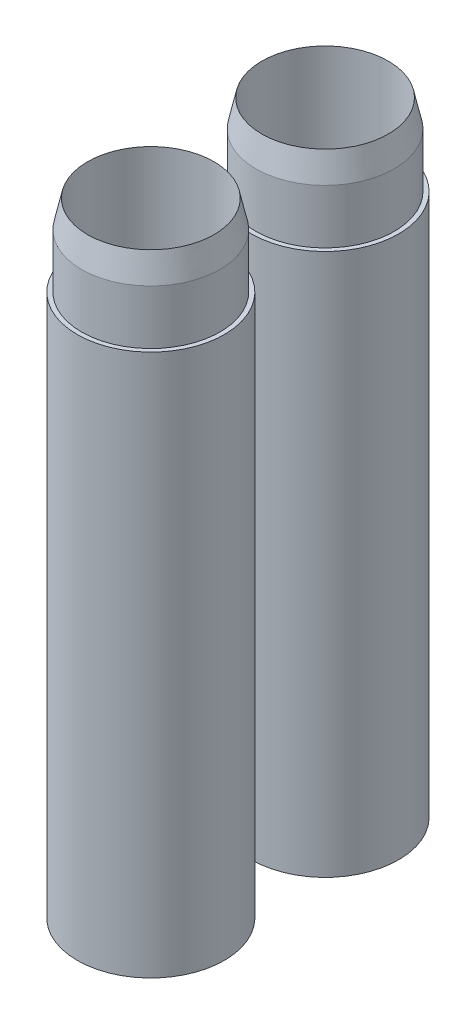
SolidWorks part; units mm, degrees
other "DetailItem1"
other "DetailItem2"
material "PLA"
ref_plane "Front Plane" through (0, 0, 0) normal (0, 0, 1) x (1, 0, 0)
ref_plane "Top Plane" through (0, 0, 0) normal (0, 1, 0) x (1, 0, 0)
ref_plane "Right Plane" through (0, 0, 0) normal (1, 0, 0) x (0, 0, -1)
sketch "Sketch1" plane through (0, 0, 0) normal (0, 1, 0) x (1, 0, 0)
  line L0 (-25.4274, 2.5) -> (-26.75, 0)
  line L1 (-26.75, 0) -> (-25.4274, -2.5)
  circle A0 centre (0, 0) radius 27.15
  arc A1 (-25.4274, -2.5) -> (-25.4274, 2.5) centre (0, 0) ccw
  dimension "D1" = 54.3
  dimension "D2" = 1.6
  dimension "D3" = 26.75
  dimension "D4" = 5
extrude "mandrel" add sketch "Sketch1" along normal blind 200 contours A0 A1 L1 L0 region at (-27.0732, 0, 0)
ref_axis "x" through (-29.7, 0, 0) along (1, 0, 0)
ref_axis "y" through (0, 200, 0) along (0, -1, 0)
ref_axis "z" through (0, 0, -29.7) along (0, 0, 1)
ref_axis "rip_tab_edge" through (-25.4274, 200, 2.5) along (0, -1, 0)
ref_plane "Plane3" through (0, 0, 0) normal (0, 0, -1) x (-1, 0, 0)
ref_plane "Plane2" through (0, 0, 0) normal (-0.0978, 0, -0.9952) x (-0.9952, 0, 0.0978)
sketch "Sketch3" plane through (0, 0, 0) normal (-0.0978, 0, -0.9952) x (-0.9952, 0, 0.0978)
  line L0 (25.55, 0) -> (20.55, 8.6603)
  line L1 (20.55, 8.6603) -> (20.55, 18.6603)
  line L2 (20.55, 18.6603) -> (25.55, 27.3205)
  line L3 (25.55, 200) -> (25.55, 0) construction
  line L4 (25.55, 27.3205) -> (25.55, 0)
  dimension "D1" = 5
  dimension "D2" = 30
  dimension "D3" = 30
  dimension "D4" = 10
sketch "Sketch4" plane through (0, 0, 0) normal (0, 0, -1) x (-1, 0, 0)
  line L2 (-23.3331, 192.2169) -> (-23.3331, 230)
  line L4 (-25.55, 190) -> (-25.55, 220)
  line L10 (-25.55, 220) -> (-23.3331, 230)
  line L11 (-23.3331, 192.2169) -> (-25.55, 190)
  line L12 (27.15, 200) -> (-27.15, 200) construction
  dimension "D2" = 25.55
  dimension "D3" = 30
  dimension "D1" = 135
  dimension "D4" = 12.5
  dimension "D5" = 10
  dimension "D6" = 10
revolve "coupler" add sketch "Sketch4" angle 360 about axis through (0, 200, 0) along (0, -1, 0)
revolve "tab" add sketch "Sketch3" angle 5 about axis through (0, 200, 0) along (0, -1, 0) reverse direction yes
sketch "Sketch5" plane through (0, 0, 0) normal (0, -1, 0) x (1, 0, 0)
  line L0 (-26.75, 0) -> (-25.4274, 2.5)
  line L1 (-25.4274, 2.5) -> (-25.4274, -2.5)
  line L2 (-25.4274, -2.5) -> (-26.75, 0) construction
  arc A0 (-25.4274, -2.5) -> (-25.4274, 2.5) centre (0, 0) ccw construction
  line M6 (-25.4274, -2.5) -> (-26.75, 0)
  line M7 (-26.75, 0) -> (-25.4274, 2.5)
extrude "Cut-Extrude1" cut sketch "Sketch5" against normal through all both and the other way through all contours L1 M7 M6 region at (-25.8683, 0, 0)
pattern_linear "LPattern1" count 2 spacing 64.3 along (0, 0, 1) of "coupler", "mandrel"
equation "\"nozzle_diameter\"= 0.4mm"
equation "\"wall_count\"= 4"
equation "\"wall_thickness\"= \"wall_count\" * \"nozzle_diameter\""
equation "\"notch_minimum\"= \"nozzle_diameter\""
equation "\"tube_id\"= 54.3mm"
equation "\"D1@Sketch1\"=\"tube_id\""
equation "\"D2@Sketch1\"=\"wall_thickness\""
equation "\"D3@Sketch1\"=(\"tube_id\"/2)-\"notch_minimum\""
equation "\"notch_width\"= 5mm"
equation "\"tube_length\"= 20"
equation "\"D1@mandrel\" = \"tube_length\""
equation "\"D2@Sketch4\"=\"tube_id\"/2-\"wall_thickness\""
equation "\"D3@LPattern1\"=\"tube_id\"+1cm"
equation "\"r_y\"= \"needed\" / 2"
